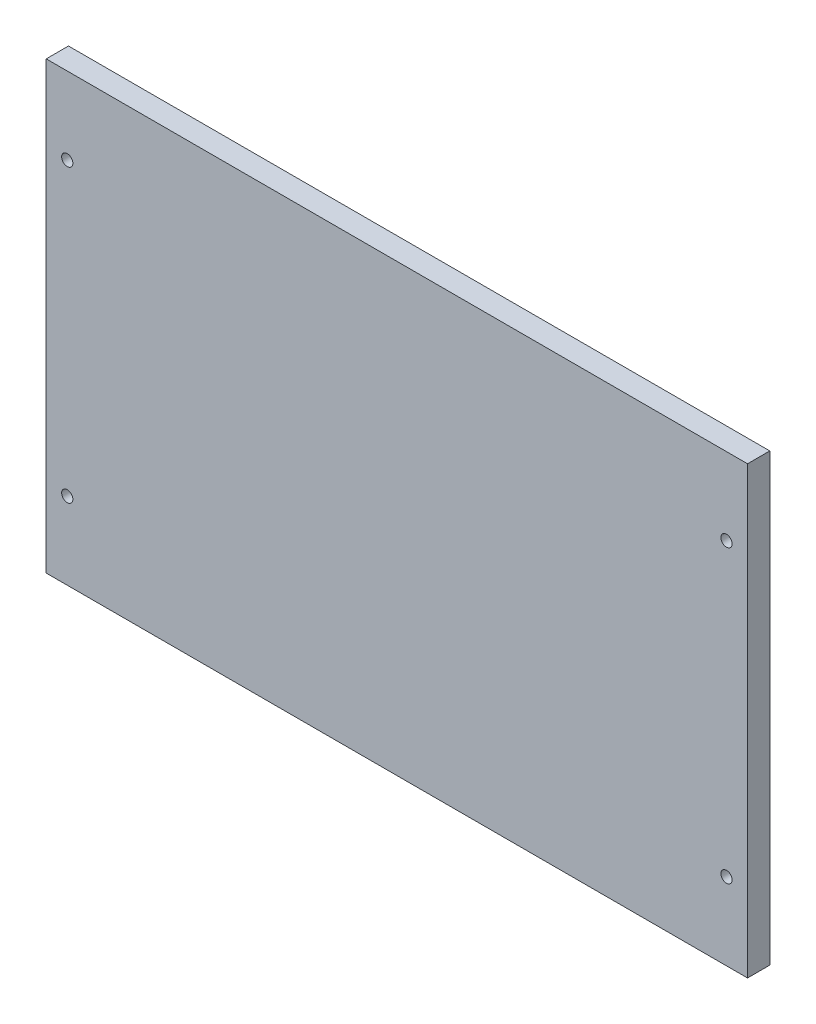
SolidWorks part; units mm, degrees
ref_plane "Front Plane" through (0, 0, 0) normal (0, 0, 1) x (1, 0, 0)
ref_plane "Top Plane" through (0, 0, 0) normal (0, 1, 0) x (1, 0, 0)
ref_plane "Right Plane" through (0, 0, 0) normal (1, 0, 0) x (0, 0, -1)
sketch "Sketch1" plane through (0, 0, 0) normal (0, 0, 1) x (1, 0, 0)
  line L0 (100, 127) -> (100, 0) construction
  line L1 (0, 0) -> (200, 0)
  line L2 (0, 0) -> (0, 127)
  line L3 (0, 127) -> (200, 127)
  line L4 (200, 0) -> (200, 127)
  line L5 (0, 63.5) -> (200, 63.5) construction
  circle A3 centre (6, 105) radius 1.6
  circle A7 centre (194, 105) radius 1.6
  circle A8 centre (194, 22) radius 1.6
  circle A9 centre (6, 22) radius 1.6
  dimension "D11" = 3.2
  dimension "D1" = 127
  dimension "D2" = 200
  dimension "D12" = 6
  dimension "D13" = 22
extrude "Wall" add sketch "Sketch1" along normal blind 6.35
sketch "Sketch2" [suppressed] plane through (0, 0, 6.35) normal (0, 0, 1) x (1, 0, 0)
  line L0 (100, 127) -> (100, 98.425) construction
  line L1 (200, 127) -> (0, 127) construction
  line L2 (100, 98.425) -> (66.6667, 98.425) construction
  line L3 (100, 98.425) -> (133.3333, 98.425) construction
  line L4 (0, 127) -> (0, 0) construction
  circle A0 centre (100, 98.425) radius 3.9687
  circle A1 centre (66.6667, 98.425) radius 3.9688
  circle A2 centre (133.3333, 98.425) radius 3.9687
  dimension "D2" = 7.9375
  dimension "D1" = 28.575
  dimension "D3" = 66.6667
extrude "RodSupportCutouts" [suppressed] cut sketch "Sketch2" against normal up to next
sketch "Sketch3" [suppressed] plane through (0, 0, 6.35) normal (0, 0, 1) x (1, 0, 0)
  line L1 (25.4, 88.9) -> (174.6, 88.9)
  line L2 (25.4, 88.9) -> (25.4, 114.3)
  line L3 (25.4, 114.3) -> (174.6, 114.3)
  line L4 (174.6, 88.9) -> (174.6, 114.3)
  line L5 (25.4, 88.9) -> (174.6, 114.3) construction
  line L6 (25.4, 114.3) -> (174.6, 88.9) construction
  line L7 (200, 127) -> (0, 127) construction
  line L8 (0, 127) -> (0, 0) construction
  point P0 (100, 101.6)
  point P9 (100, 127)
  dimension "D1" = 25.4
  dimension "D2" = 25.4
  dimension "D3" = 25.4
extrude "CannulaLargeCutout" [suppressed] cut sketch "Sketch3" against normal up to next
sketch "Sketch4" [suppressed] plane through (0, 0, 9.525) normal (0, 0, 1) x (1, 0, 0)
  line L0 (6, 103.5) -> (194, 103.5) construction
  line L1 (6, 105) -> (6, 22) construction
  line L2 (194, 105) -> (194, 22) construction
  line L3 (200, 127) -> (0, 127) construction
  line L4 (0, 127) -> (0, 0) construction
  circle A0 centre (60, 103.5) radius 6.35
  circle A1 centre (20, 103.5) radius 6.35
  circle A2 centre (100, 103.5) radius 6.35
  circle A3 centre (140, 103.5) radius 6.35
  circle A4 centre (60, 63.5) radius 6.35
  circle A5 centre (100, 63.5) radius 6.35
  circle A6 centre (140, 63.5) radius 6.35
  circle A7 centre (60, 23.5) radius 6.35
  circle A8 centre (100, 23.5) radius 6.35
  circle A9 centre (140, 23.5) radius 6.35
  circle A10 centre (20, 63.5) radius 6.35
  circle A11 centre (20, 23.5) radius 6.35
  circle A12 centre (180, 103.5) radius 6.35
  circle A13 centre (180, 63.5) radius 6.35
  circle A14 centre (180, 23.5) radius 6.35
  point P42 (100, 127)
  point P45 (0, 63.5)
  dimension "D3" = 12.7
  dimension "D1" = 5
  dimension "D2" = 3
extrude "CannulaHoles" [suppressed] cut sketch "Sketch4" against normal up to next
equation "\"Length\"= 283mm"
equation "\"Width\"= 225mm"
equation "\"WallThickness\"= 0.25in"
equation "\"UpperWaterJacketThickness\"= 28mm"
equation "\"SpacerHeight\"= 80.2mm"
equation "\"SpacerCornerWidth\"= 10mm"
equation "\"SpacerCornerHeight\"= 60.16mm"
equation "\"SpacerPegDiameter\"= 10mm"
equation "\"SpacerPegHeight\"= 10mm"
equation "\"TubingShort\"= 110mm"
equation "\"TubingLong\"= 175mm"
equation "\"PlateLength\"= 252mm"
equation "\"PlateWidth\"= 190mm"
equation "\"PlateHoleDiameter\"= 5.9mm"
equation "\"PlateHoleBottom\"= 2mm"
equation "\"PlateHoleSide\"= 1.55mm"
equation "\"PlateHoleSpacing\"= 3.1mm"
equation "\"PlateThickness\"= 1.55mm"
equation "\"ReservoirBottom\"= 12.5mm"
equation "\"ReservoirSupportWidth\"= 12mm"
equation "\"ReservoirSupportHeight\"= 15.1mm"
equation "\"ReservoirSupportPlacementHeight\"= 50mm"
equation "\"ReservoirHoleDiameter\"= 12.7mm"
equation "\"ReservoirHoleRight\"= 25mm"
equation "\"ReservoirHoleTop\"= \"ReservoirSupportPlacementHeight\""
equation "\"ReservoirHeight\"= 90mm"
equation "\"ReservoirPortBottom\"= 4mm"
equation "\"ReservoirPortTop\"= 10mm"
equation "\"ReservoirPortWidth\"= 101mm"
equation "\"CustomSpacerHeight\"= 5in"
equation "\"CustomSpacerRodHoleHeight\"= .75in"
equation "\"CustomSpacerRodHoleDiameter\"= .3125in"
equation "\"ScrewBlockSide\"= 12mm"
equation "\"ScrewBlockUpperHeight\"= 16mm"
equation "\"ScrewBlockLowerHeight\"= 16mm"
equation "\"InternalLength\"= 258mm"
equation "\"InternalWidth\"= 200mm"
equation "\"CustomSpacerPegHeight\"= 1in"
equation "\"CustomSpacerScrewBore\"=3.2mm"
equation "\"CustomSpacerScrewDepth\"=10mm"
equation "\"D1@Sketch1\"=\"CustomSpacerHeight\""
equation "\"D2@Sketch1\"=\"WallLength\""
equation "\"D11@Sketch1\"=\"CustomSpacerScrewBore\""
equation "\"D12@Sketch1\" = \"ScrewBlockSide\"/2"
equation "\"D13@Sketch1\"=\"ScrewBlockUpperHeight\"+\"ScrewBlockSide\"/2"
equation "\"D1@Wall\" = \"WallThickness\""
equation "\"D1@Sketch2\"=\"CustomSpacerRodHoleHeight\" + \"CustomSpacerRodHoleDiameter\" +0.0625in"
equation "\"D2@Sketch2\"=\"CustomSpacerRodHoleDiameter\""
equation "\"D3@Sketch2\"=\"InternalWidth\" / 3"
equation "\"D1@Sketch3\"=1in"
equation "\"WallLength\"= \"InternalWidth\""
